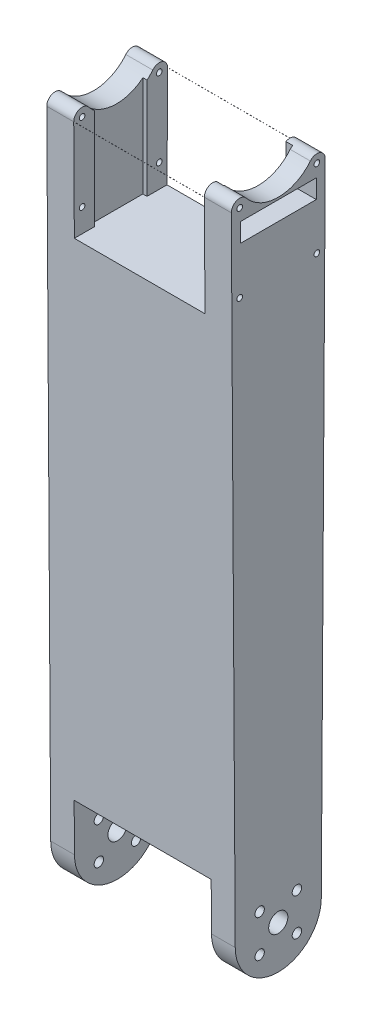
SolidWorks part; units mm, degrees
ref_plane "Front Plane" through (0, 0, 0) normal (0, 0, 1) x (1, 0, 0)
ref_plane "Top Plane" through (0, 0, 0) normal (0, 1, 0) x (1, 0, 0)
ref_plane "Right Plane" through (0, 0, 0) normal (1, 0, 0) x (0, 0, -1)
sketch "Sketch1" plane through (0, 0, 0) normal (1, 0, 0) x (0, 0, -1)
  line L0 (55.88, 0) -> (-55.88, 0) construction
  line L1 (-32.73, 0) -> (12.5, 0) construction
  line L2 (-32.73, 0) -> (-32.73, -36.5) construction
  line L3 (-32.73, -36.5) -> (12.5, -36.5) construction
  line L4 (12.5, 0) -> (12.5, -36.5) construction
  line L5 (0, 38.1) -> (0, 215.9) construction
  line L6 (-50.8, 0) -> (50.8, 0) construction
  line L7 (-50.8, 0) -> (-50.8, -50.8) construction
  line L8 (-50.8, -50.8) -> (50.8, -50.8) construction
  line L9 (50.8, 0) -> (50.8, -50.8) construction
  line L10 (0, 55.88) -> (0, -55.88) construction
  line L11 (0, 215.9) -> (-75.29, 422.7577) construction
  line L12 (-67.0833, 436.5088) -> (-90.4159, 428.0165) construction
  line L13 (12.415, 180.785) -> (-12.415, 180.785) construction
  line L18 (12.415, 180.785) -> (12.415, 226.015) construction
  line L19 (-12.415, 180.785) -> (-12.415, 226.015) construction
  line L20 (12.415, 226.015) -> (-12.415, 226.015) construction
  line L21 (0, 215.9) -> (0, 180.785) construction
  line L22 (0, 203.4) -> (-12.415, 203.4) construction
  line L27 (-67.0833, 436.5088) -> (-51.6137, 394.0065) construction
  line L28 (-90.4159, 428.0165) -> (-74.9463, 385.5142) construction
  line L29 (-51.6137, 394.0065) -> (-74.9463, 385.5142) construction
  line L30 (-59.3485, 415.2577) -> (-82.6811, 406.7653) construction
  line L31 (-75.29, 422.7577) -> (-133.6626, 471.7381) construction
  line L33 (-12.415, 50.6) -> (12.415, 50.6) construction
  line L34 (-12.415, 50.6) -> (-12.415, 5.37) construction
  line L35 (-12.415, 5.37) -> (12.415, 5.37) construction
  line L36 (12.415, 50.6) -> (12.415, 5.37) construction
  circle A0 centre (0, 38.1) radius 3 construction
  circle A1 centre (0, 215.9) radius 3 construction
  circle A3 centre (-75.29, 422.7577) radius 3 construction
  point P6 (-10.115, -36.5)
  point P9 (0, -50.8)
  point P25 (-12.5, 38.1)
  point P27 (0, 203.4)
  point P42 (-63.28, 389.7604)
  point P47 (0, 5.37)
  dimension "D15" = 6
  dimension "D8" = 0
  dimension "D12" = 12.5
  dimension "D1" = 36.5
  dimension "D2" = 45.23
  dimension "D3" = 101.6
  dimension "D4" = 50.8
  dimension "D5" = 38.1
  dimension "D6" = 177.8
  dimension "D7" = 220.1333
  dimension "D9" = 24.83
  dimension "D10" = 12.5
  dimension "D11" = 12.5
  dimension "D13" = 76.2
  dimension "D14" = 160
  dimension "D16" = 12.5
  dimension "D17" = 150
  dimension "D18" = 12.5
sketch "Sketch2" plane through (0, 0, 0) normal (0, 0, 1) x (1, 0, 0)
  line L6 (55.88, 0) -> (-55.88, 0) construction
  line L7 (-50.8, 0) -> (50.8, 0) construction
  line L8 (-50.8, 0) -> (-50.8, -50.8) construction
  line L9 (-50.8, -50.8) -> (50.8, -50.8) construction
  line L10 (50.8, 0) -> (50.8, -50.8) construction
  dimension "D1" = 101.6
sketch "Sketch3" plane through (0, 0, 0) normal (1, 0, 0) x (0, 0, -1)
  line L0 (-11.4298, 38.0297) -> (-12.4725, 207.5865)
  line L1 (-10.25, 9.1002) -> (10.25, 9.1002) construction
  line L3 (-10.25, 186.9002) -> (10.25, 186.9002) construction
  line L4 (0, 215.9) -> (-75.29, 422.7577) construction
  line L5 (12.4725, 207.5865) -> (11.4298, 38.0297)
  circle A0 centre (0, 38.1) radius 10
  circle A1 centre (-10.25, 9.1002) radius 0.7501
  circle A2 centre (10.25, 9.1002) radius 0.7501
  circle A3 centre (10.25, 29.8002) radius 0.7501
  circle A4 centre (-10.25, 29.8002) radius 0.7501
  circle A5 centre (-4.9497, 43.0497) radius 1.2501
  circle A6 centre (4.9497, 43.0497) radius 1.2501
  circle A7 centre (4.9497, 33.1503) radius 1.2501
  circle A8 centre (-4.9497, 33.1503) radius 1.2501
  circle A9 centre (-10.25, 186.9002) radius 0.7501
  circle A10 centre (10.25, 186.9002) radius 0.7501
  circle A11 centre (10.25, 207.6001) radius 0.7501
  circle A12 centre (-10.25, 207.6001) radius 0.7501
  circle A13 centre (0, 215.9) radius 10 construction
  arc A14 (-8.5228, 208.9988) -> (8.5228, 208.9988) centre (0, 215.9) ccw
  arc A16 (8.5228, 208.9988) -> (12.4725, 207.5865) centre (10.25, 207.6001) cw
  arc A17 (-11.4298, 38.0297) -> (11.4298, 38.0297) centre (0, 38.1) ccw
  circle A18 centre (0, 38.1) radius 2.54
  arc A19 (-8.5228, 208.9988) -> (-12.4725, 207.5865) centre (-10.25, 207.6001) ccw
  point P5 (0, 186.9002)
  point P16 (0, 9.1002)
  point P35 (0, 0)
  point P36 (0, 0)
  point P41 (0, 0)
  dimension "D1" = 1.5001
  dimension "D9" = 20
  dimension "D12" = 2.5001
  dimension "D13" = 20.7
  dimension "D16" = 0
  dimension "D17" = 5.08
  dimension "D18" = 11.43
  dimension "D19" = 2.2225
  dimension "D4" = 13.189
  dimension "D5" = 28.9998
  dimension "D6" = 20.5001
  dimension "D7" = 20.7
  dimension "D8" = 28.9998
  dimension "D10" = 7
  dimension "D14" = 20.5
  dimension "D15" = 13.189
  dimension "D2" = 2
  dimension "D3" = 2
  dimension "D11" = 4
extrude "Boss-Extrude1" add sketch "Sketch3" along normal blind 24.511 and the other way blind 24.511 contours A17 L5 A16 A14 A19 L0
extrude "Cut-Extrude3" cut sketch "Sketch3<4>" against normal through all and the other way through all contours A8 | A5 | A6 | A7 | A9 | A10 | A11 | A12 | A18
sketch "Sketch3<4>" plane through (0, 0, 0) normal (1, 0, 0) x (0, 0, -1) same geometry as "Sketch3"
sketch "Sketch4" plane through (0, 0, 0) normal (1, 0, 0) x (0, 0, -1)
  line L0 (-12.415, 50.6) -> (12.415, 50.6) construction
  line L1 (-11.5071, 50.6) -> (11.5071, 50.6)
  line L2 (-11.5071, 50.6) -> (-11.5071, 26.67)
  line L3 (-11.5071, 26.67) -> (11.5071, 26.67)
  line L4 (11.5071, 50.6) -> (11.5071, 26.67)
  line L5 (-11.4298, 38.0297) -> (-12.4725, 207.5865) construction
  line L6 (12.4725, 207.5865) -> (11.4298, 38.0297) construction
  line L8 (-12.4725, 180.7002) -> (12.4725, 180.7002)
  line L9 (-12.4725, 180.7002) -> (-12.4725, 209.8226)
  line L10 (-12.4725, 209.8226) -> (12.4725, 209.8226)
  line L11 (12.4725, 180.7002) -> (12.4725, 209.8226)
  arc A0 (-11.4298, 38.0297) -> (11.4298, 38.0297) centre (0, 38.1) ccw construction
  arc A2 (-8.5228, 208.9988) -> (-12.4725, 207.5865) centre (-10.25, 207.6001) ccw construction
  dimension "D1" = 6.2
extrude "Cut-Extrude4" cut sketch "Sketch4" against normal blind 18.2 and the other way blind 18.2 contours L4 L1 L2 L3 region at (0, 38.635, 0)
extrude "Cut-Extrude5" cut sketch "Sketch4<4>" against normal blind 17.35 and the other way blind 17.35 contours L8 L11 L10 L9 region at (0, 195.2614, 0)
sketch "Sketch4<4>" plane through (0, 0, 0) normal (1, 0, 0) x (0, 0, -1) same geometry as "Sketch4"
sketch "Sketch5" plane through (17.35, 0, 0) normal (-1, 0, 0) x (0, 0, 1)
  line L0 (-11.9981, 210.6001) -> (-11.9981, 208.7639)
  line L1 (-11.9981, 206.4364) -> (-11.9981, 184.2639)
  line L2 (-9.6037, 181.1021) -> (9.6037, 181.1021)
  line L3 (11.9981, 184.2639) -> (11.9981, 206.4364)
  line L4 (11.9981, 208.7639) -> (11.9981, 210.6001)
  line L5 (11.9981, 210.6001) -> (9.645, 210.6001)
  line L6 (6.5, 207.0195) -> (6.5, 204.3501)
  line L7 (6.5, 204.3501) -> (10.1, 204.3501)
  line L8 (10.1, 204.3501) -> (10.1, 199.3501)
  line L9 (10.1, 199.3501) -> (9.2, 199.3501)
  line L10 (9.2, 199.3501) -> (9.2, 186.0001)
  line L11 (9.2, 186.0001) -> (-9.2, 186.0001)
  line L12 (-9.2, 186.0001) -> (-9.2, 199.3501)
  line L13 (-9.2, 199.3501) -> (-10.1, 199.3501)
  line L14 (-10.1, 199.3501) -> (-10.1, 204.3501)
  line L15 (-10.1, 204.3501) -> (-6.5, 204.3501)
  line L16 (-6.5, 204.3501) -> (-6.5, 207.0195)
  line L17 (-9.645, 210.6001) -> (-11.9981, 210.6001)
  line L19 (-10.1, 204.3501) -> (10.1, 204.3501)
  line L20 (-10.1, 204.3501) -> (-10.1, 199.3501)
  line L21 (-10.1, 199.3501) -> (10.1, 199.3501)
  line L22 (10.1, 204.3501) -> (10.1, 199.3501)
  line L23 (9.2, 186.0001) -> (-9.2, 186.0001)
  line L24 (9.2, 186.0001) -> (9.2, 199.3501)
  line L25 (9.2, 199.3501) -> (-9.2, 199.3501)
  line L26 (-9.2, 186.0001) -> (-9.2, 199.3501)
  line L27 (-9.2, 199.3501) -> (9.2, 199.3501)
  line L28 (-9.2, 199.3501) -> (-9.2, 210.6001)
  line L29 (-9.2, 210.6001) -> (9.2, 210.6001)
  line L30 (9.2, 199.3501) -> (9.2, 210.6001)
  arc A0 (-11.9981, 208.7639) -> (-11.9981, 206.4364) centre (-10.25, 207.6001) ccw
  arc A1 (-11.9981, 184.2639) -> (-9.6037, 181.1021) centre (-10.25, 183.1001) ccw
  arc A2 (9.6037, 181.1021) -> (11.9981, 184.2639) centre (10.25, 183.1001) ccw
  arc A3 (11.9981, 206.4364) -> (11.9981, 208.7639) centre (10.25, 207.6001) ccw
  arc A4 (6.5, 207.0195) -> (9.645, 210.6001) centre (0, 215.9001) ccw
  arc A5 (-9.645, 210.6001) -> (-6.5, 207.0195) centre (0, 215.9001) ccw
  point P32 (0, 0)
  arc M30 (12.4725, 207.6138) -> (8.5228, 208.9988) centre (10.25, 207.6001) ccw
  arc M31 (8.5228, 208.9988) -> (-8.5228, 208.9988) centre (0, 215.9) cw
  arc M32 (-8.5228, 208.9988) -> (-12.4725, 207.6138) centre (-10.25, 207.6001) ccw
extrude "Cut-Extrude6" cut sketch "Sketch5" against normal blind 18.2 contours L20 L19 L22 L21
extrude "Cut-Extrude7" cut sketch "Sketch5<3>" against normal blind 1.8 contours L21 L12 L11 L10 | A5 L16 L19 L6 A4 M32 M30 M31 | A5 L28 L19 L16 M32 | A4 L6 L7 L30 M30 region at (17.35, 206.3775, -8.0053) region at (17.35, 209.128, -8.6612) region at (17.35, 192.6751, 0) region at (17.35, 206.3775, 8.0053)
sketch "Sketch5<3>" plane through (17.35, 0, 0) normal (-1, 0, 0) x (0, 0, 1) same geometry as "Sketch5"
sketch "Sketch6" plane through (-17.35, 0, 0) normal (1, 0, 0) x (0, 0, -1)
  line L0 (-12.3071, 180.7002) -> (12.3071, 180.7002) construction
  line L1 (7, 180.7002) -> (-7, 180.7002)
  line L2 (7, 180.7002) -> (7, 209.8226)
  line L3 (7, 209.8226) -> (-7, 209.8226)
  line L4 (-7, 180.7002) -> (-7, 209.8226)
  arc A0 (-8.5228, 208.9988) -> (-12.4725, 207.6138) centre (-10.25, 207.6001) ccw construction
  point P6 (0, 180.7002)
  point P7 (0, 0)
  point P8 (0, 209.8226)
  dimension "D1" = 14
extrude "Cut-Extrude8" cut sketch "Sketch6" against normal blind 1.1
